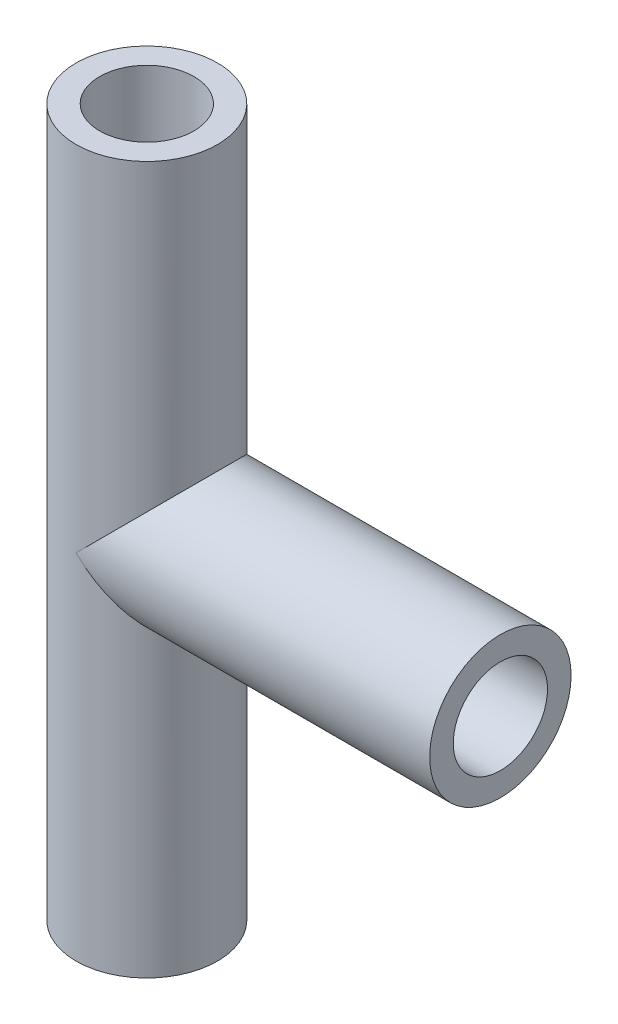
SolidWorks part; units mm, degrees
ref_plane "Front Plane" through (0, 0, 0) normal (0, 0, 1) x (1, 0, 0)
ref_plane "Top Plane" through (0, 0, 0) normal (0, 1, 0) x (1, 0, 0)
ref_plane "Right Plane" through (0, 0, 0) normal (1, 0, 0) x (0, 0, -1)
sketch "Sketch4" plane through (0, 0, 0) normal (0, 1, 0) x (1, 0, 0)
  circle A0 centre (0, 0) radius 3
  dimension "D1" = 6
extrude "Boss-Extrude2" add sketch "Sketch4" along normal blind 15 and the other way blind 15
sketch "Sketch5" plane through (0, 0, 0) normal (1, 0, 0) x (0, 0, -1)
  circle A0 centre (0, 0) radius 3
  dimension "D1" = 6
extrude "Boss-Extrude3" add sketch "Sketch5" along normal blind 15
sketch "Sketch6" plane through (0, -15, 0) normal (0, -1, 0) x (1, 0, 0)
  circle A0 centre (0, 0) radius 2
  circle A1 centre (0, 0) radius 3 construction
  point P5 (0, 0)
  dimension "D1" = 1
extrude "Cut-Extrude1" cut sketch "Sketch6" against normal through all
sketch "Sketch7" plane through (15, 0, 0) normal (1, 0, 0) x (0, 0, -1)
  circle A0 centre (0, 0) radius 2
  arc A1 (3, 0) -> (-3, 0) centre (0, 0) ccw construction
  dimension "D1" = 1
extrude "Cut-Extrude2" cut sketch "Sketch7" against normal blind 15
